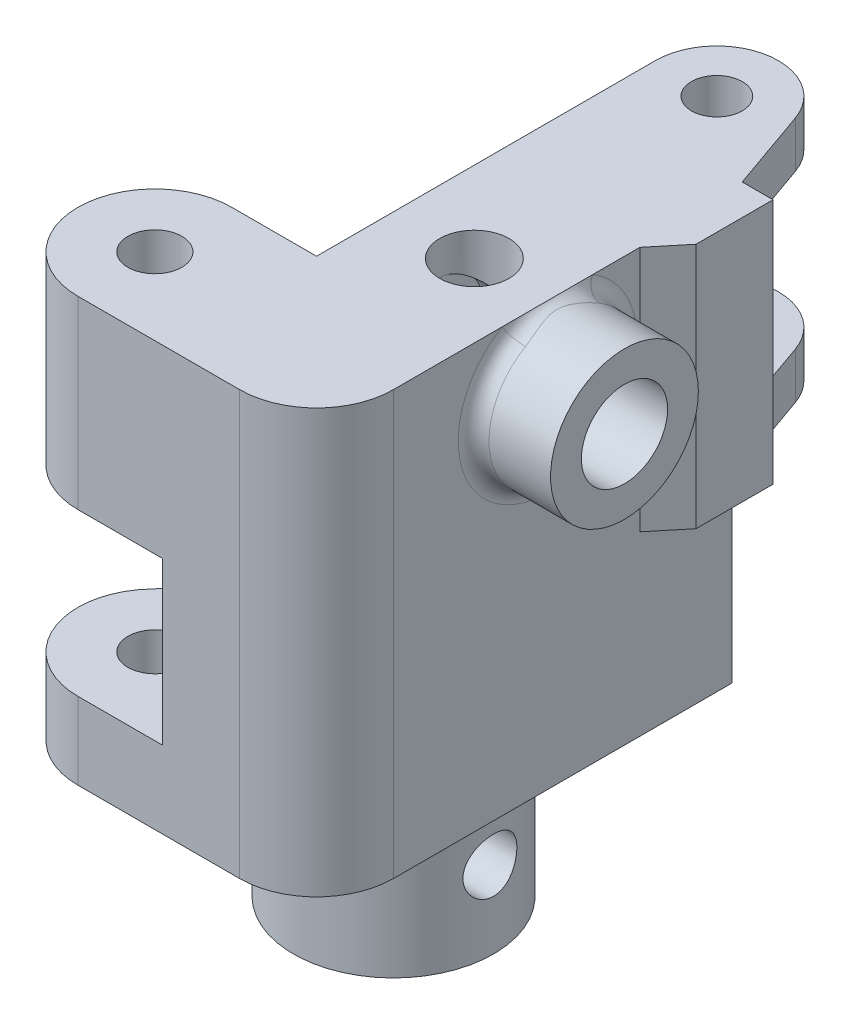
SolidWorks part; units mm, degrees
ref_plane "Front Plane" through (0, 0, 0) normal (0, 0, 1) x (1, 0, 0)
ref_plane "Top Plane" through (0, 0, 0) normal (0, 1, 0) x (1, 0, 0)
ref_plane "Right Plane" through (0, 0, 0) normal (1, 0, 0) x (0, 0, -1)
sketch "Sketch1" plane through (0, 0, 0) normal (0, 1, 0) x (1, 0, 0)
  line L0 (0, 0) -> (5.5, 0) construction
  line L1 (0, 5) -> (5.5, 5)
  line L2 (0, -5) -> (5.5, -5)
  line L3 (5.5, 5) -> (5.5, 22)
  line L4 (5.5, -5) -> (15.5, -5)
  line L6 (5.5, 22) -> (15.5, 22)
  line L7 (15.5, -5) -> (15.5, 22)
  line L8 (5.5, 20) -> (15.5, 20) construction
  arc A0 (0, 5) -> (0, -5) centre (0, 0) ccw
  circle A2 centre (0, 0) radius 1.75
  circle A3 centre (5.5, 10) radius 39 construction
  dimension "D1" = 5
  dimension "D2" = 3.5
  dimension "D5" = 78
  dimension "D3" = 5.5
  dimension "D4" = 10
  dimension "D6" = 10
  dimension "D7" = 10
  dimension "D8" = 2
extrude "Boss-Extrude1" add sketch "Sketch1" along normal blind 5
sketch "Sketch2" plane through (0, 5, 0) normal (0, 1, 0) x (1, 0, 0)
  line L1 (5.5, 22) -> (15.5, 22)
  line L2 (5.5, 22) -> (5.5, -5)
  line L3 (5.5, -5) -> (15.5, -5)
  line L4 (15.5, 22) -> (15.5, -5)
extrude "Boss-Extrude2" add sketch "Sketch2" along normal blind 10.5
sketch "Sketch3" plane through (0, 15.5, 0) normal (0, 1, 0) x (1, 0, 0)
  line L0 (5.5, 5) -> (15.5, 5)
  line L3 (5.5, -5) -> (5.5, 5)
  line L4 (5.5, 22) -> (5.5, -5)
  line L5 (5.5, -5) -> (15.5, -5)
  line L6 (15.5, -5) -> (15.5, 22)
  line L7 (15.5, 22) -> (5.5, 22)
  line L9 (5.5, -5) -> (15.5, -5)
  line L10 (15.5, -5) -> (15.5, 5)
  line L12 (5.5, 5) -> (0, 5)
  line L13 (0, -5) -> (5.5, -5)
  line L15 (5.5, 5) -> (0, 5)
  line L16 (0, -5) -> (5.5, -5)
  circle A0 centre (0, 0) radius 1.75 construction
  arc A1 (0, 5) -> (0, -5) centre (0, 0) ccw
  arc A2 (0, 5) -> (0, -5) centre (0, 0) ccw
  circle A3 centre (0, 0) radius 1.75
  dimension "D1" = 0
  dimension "D2" = 0
extrude "Boss-Extrude3" add sketch "Sketch3" along normal blind 5
fillet "Fillet1" radius 5 1 edges at (15.5, 10.25, 5)
sketch "Sketch4" plane through (15.5, 0, 0) normal (1, 0, 0) x (0, 0, -1)
  line L0 (1.75, 20.5) -> (-1.75, 20.5) construction
  line L1 (1.75, 20.5) -> (-1.75, 20.5)
  line L2 (0, 20.5) -> (0, 10.25) construction
  line L3 (0, 20.5) -> (0, 0) construction
  line L4 (0, 10.25) -> (20, 10.25) construction
  circle A0 centre (20, 10.25) radius 2.8 construction
  dimension "D2" = 5.6
  dimension "D1" = 20
extrude "Cut-Extrude1" [suppressed] cut sketch "Sketch4" against normal through all contours A0
sketch "Sketch5" plane through (0, 0, 0) normal (0, -1, 0) x (1, 0, 0)
  line L0 (5.5, -22) -> (5.5, -5) construction
  circle A0 centre (5.5, -10) radius 6.5
  circle A1 centre (0, 0) radius 1.75 construction
  circle A2 centre (0, 0) radius 1.75 construction
  circle A3 centre (5.5, -10) radius 2.5
  dimension "D2" = 13
  dimension "D3" = 5
  dimension "D1" = 10
extrude "Boss-Extrude4" add sketch "Sketch5" along normal blind 11
sketch "Sketch6" plane through (0, 0, 0) normal (0, 1, 0) x (1, 0, 0)
  line L3 (5.5, 12.5) -> (5.5, 16.5)
  line L4 (1.3467, 5) -> (5.5, 5)
  line L5 (5.5, 5) -> (5.5, 7.5)
  line L6 (5.5, 12.5) -> (5.5, 16.5)
  line L7 (1.3467, 5) -> (5.5, 5)
  line L8 (5.5, 5) -> (5.5, 7.5)
  arc A2 (5.5, 16.5) -> (1.3467, 5) centre (5.5, 10) ccw
  arc A3 (5.5, 12.5) -> (5.5, 7.5) centre (5.5, 10) ccw
  arc A4 (5.5, 16.5) -> (1.3467, 5) centre (5.5, 10) ccw
  arc A5 (5.5, 12.5) -> (5.5, 7.5) centre (5.5, 10) ccw
  dimension "D1" = 0
extrude "Boss-Extrude5" add sketch "Sketch6" along normal up to surface (5 mm away) up to face at (1.5, 5, 0)
sketch "Sketch7" plane through (0, 0, 0) normal (1, 0, 0) x (0, 0, -1)
  line L0 (10, -11) -> (10, -6) construction
  line L1 (3.5, -11) -> (16.5, -11) construction
  circle A0 centre (10, -6) radius 1.75
  dimension "D1" = 3.5
  dimension "D2" = 5
extrude "Cut-Extrude2" cut sketch "Sketch7" against normal through all both and the other way through all
sketch "Sketch8" [suppressed] plane through (15.5, 0, 0) normal (1, 0, 0) x (0, 0, -1)
  circle A0 centre (13.5, 10.25) radius 1.6
  circle A1 centre (26.5, 10.25) radius 1.6
  circle A2 centre (20, 10.25) radius 2.8 construction
  circle A3 centre (20, 10.25) radius 2.8 construction
  dimension "D2" = 3.2
  dimension "D3" = 3.2
  dimension "D1" = 6.5
  dimension "D4" = 6.5
extrude "Cut-Extrude3" [suppressed] cut sketch "Sketch8" against normal blind 8
fillet "Fillet2" [suppressed] radius 5
chamfer "Chamfer1" [suppressed] distance 1 angle 45
fillet "Fillet3" radius 5 1 edges at (10.5, 15.5, -5)
sketch "Sketch9" plane through (5.5, 0, 0) normal (-1, 0, 0) x (0, 0, 1)
  line L0 (-22, 15.5) -> (-10, 15.5) construction
  line L1 (-22, 15.5) -> (-5, 15.5)
  line L2 (-22, 15.5) -> (-22, 27.5)
  line L3 (-22, 27.5) -> (-5, 27.5)
  line L4 (-5, 15.5) -> (-5, 27.5)
  line L5 (-5, 20.5) -> (-5, 15.5) construction
  line L7 (-22, 15.5) -> (-22, 0) construction
  dimension "D1" = 12
extrude "Boss-Extrude6" add sketch "Sketch9" against normal up to surface (10 mm away) up to face at (15.5, 11.8274, -9.6607)
fillet "Fillet4" [suppressed] radius 4
fillet "Fillet5" [suppressed] radius 2
sketch "Sketch10" [suppressed] plane through (0, 27.5, 0) normal (0, 1, 0) x (1, 0, 0)
  line L0 (10.5, 11.1) -> (10.5, 7) construction
  line L1 (5.5, 7) -> (15.5, 7) construction
  line L2 (10.5, 11.1) -> (5.5, 11.1) construction
  line L3 (5.5, 7) -> (5.5, 15.2) construction
  line L5 (9.5, 13.35) -> (11.5, 13.35) construction
  line L6 (9.5, 13.35) -> (9.5, 8.85) construction
  line L7 (9.5, 8.85) -> (11.5, 8.85) construction
  line L8 (11.5, 13.35) -> (11.5, 8.85) construction
  line L9 (9.5, 13.35) -> (11.5, 8.85) construction
  line L10 (9.5, 8.85) -> (11.5, 13.35) construction
  circle A1 centre (10.5, 11.1) radius 2
  dimension "D1" = 4.5
  dimension "D3" = 4
  dimension "D2" = 2
extrude "Cut-Extrude4" [suppressed] cut sketch "Sketch10" against normal blind 10
sketch "Sketch11" plane through (15.5, 0, 0) normal (1, 0, 0) x (0, 0, -1)
  line L0 (10, 22.5) -> (10, 27.5) construction
  line L2 (5, 27.5) -> (5, 20.5) construction
  circle A0 centre (10, 22.5) radius 2.8
  dimension "D1" = 5.6
  dimension "D2" = 5
  dimension "D3" = 5
extrude "Cut-Extrude5" cut sketch "Sketch11" against normal blind 7
sketch "Sketch12" plane through (15.5, 0, 0) normal (1, 0, 0) x (0, 0, -1)
  circle A0 centre (10, 22.5) radius 2.8 construction
  circle A1 centre (10, 22.5) radius 2.8
  circle A2 centre (10, 22.5) radius 4.8
  dimension "D1" = 2
extrude "Boss-Extrude7" add sketch "Sketch12" along normal blind 5
chamfer "Chamfer2" distance 3 angle 45 1 edges at (5.5, -11, -12.5)
chamfer "Chamfer3" distance 3 angle 45 1 edges at (5.5, 0, -10)
fillet "Fillet6" radius 2 1 edges at (3, 5, -10)
sketch "Sketch13" [suppressed] plane through (5.5, 0, 0) normal (-1, 0, 0) x (0, 0, 1)
  line L0 (-26, 15.5) -> (-17.2, 15.5) construction
  line L1 (-26, 0) -> (-37, 0)
  line L2 (-26, 0) -> (-26, 15.5)
  line L3 (-26, 15.5) -> (-37, 15.5)
  line L4 (-41, 4) -> (-41, 11.5)
  line L5 (-16.5, 5) -> (-16.5, 0) construction
  circle A0 centre (-35, 10.25) radius 2.8
  arc A3 (-37, 0) -> (-41, 4) centre (-37, 4) cw
  arc A4 (-37, 15.5) -> (-41, 11.5) centre (-37, 11.5) ccw
  dimension "D1" = 5.6
  dimension "D3" = 4
  dimension "D2" = 18.5
  dimension "D4" = 6
  dimension "D5" = 10.25
extrude "Boss-Extrude8" [suppressed] add sketch "Sketch13" against normal up to surface (10 mm away)
sketch "Sketch14" plane through (0, 20.5, 0) normal (0, 1, 0) x (1, 0, 0)
  line L4 (0, -5) -> (10.5, -5)
  line L5 (15.5, 0) -> (15.5, 5)
  line L6 (15.5, 5) -> (5.5, 5)
  line L7 (5.5, 5) -> (0, 5)
  line L8 (0, -5) -> (10.5, -5)
  line L9 (15.5, 0) -> (15.5, 5)
  line L11 (5.5, 5) -> (0, 5)
  line L13 (15.5, 5) -> (5.5, 5)
  circle A0 centre (0, 0) radius 1.75 construction
  circle A1 centre (0, 0) radius 1.75
  arc A2 (10.5, -5) -> (15.5, 0) centre (10.5, 0) ccw
  arc A3 (0, 5) -> (0, -5) centre (0, 0) ccw
  arc A4 (10.5, -5) -> (15.5, 0) centre (10.5, 0) ccw
  arc A5 (0, 5) -> (0, -5) centre (0, 0) ccw
  dimension "D1" = 0
extrude "Boss-Extrude9" add sketch "Sketch14" along normal up to surface (7 mm away) up to face at (10.5, 27.5, -13.5)
fillet "Fillet7" radius 10 1 edges at (1.3467, 2.5, -5)
fillet "Fillet8" [suppressed] radius 5
sketch "Sketch15" plane through (0, 27.5, 0) normal (0, 1, 0) x (1, 0, 0)
  line L0 (8.5, 7.2) -> (8.5, 12.8) construction
  line L1 (8.5, 7.2) -> (8.5, 12.8) construction
  line L2 (10.75, 10) -> (8.5, 10) construction
  circle A0 centre (10.75, 10) radius 2.25
  dimension "D1" = 4.5
extrude "Cut-Extrude6" cut sketch "Sketch15" against normal blind 10
fillet "Fillet9" radius 1 1 edges at (15.5, 22.5, -5.2)
sketch "Sketch16" plane through (0, 27.5, 0) normal (0, 1, 0) x (1, 0, 0)
  line L0 (5.5, 22) -> (5.5, 27)
  line L1 (13.2732, 28.3278) -> (15.5, 22)
  line L2 (5.5, 22) -> (15.5, 22)
  circle A0 centre (9.5, 27) radius 1.65
  arc A1 (13.2732, 28.3278) -> (5.5, 27) centre (9.5, 27) ccw
  dimension "D1" = 3.3
  dimension "D2" = 8
  dimension "D3" = 5
extrude "Boss-Extrude10" add sketch "Sketch16" against normal blind 16
ref_plane "Plane1" through (0, 19.5, 0) normal (0, 1, 0) x (1, 0, 0)
sketch "Sketch17" plane through (0, 19.5, 0) normal (0, 1, 0) x (1, 0, 0)
  line L0 (15.5, 22) -> (5.5, 22)
  line L1 (5.5, 5) -> (5.5, 27) construction
  line L9 (15.5, 12.9394) -> (15.5, 22)
  line L10 (15.5, 22) -> (13.2732, 28.3278)
  line L11 (5.5, 27) -> (5.5, 5)
  line L12 (5.5, 5) -> (0, 5)
  line L13 (0, -5) -> (10.5, -5)
  line L14 (15.5, 0) -> (15.5, 7.0606)
  line L15 (15.5, 7.0606) -> (15.5, 12.9394)
  line L17 (15.5, 22) -> (13.2732, 28.3278)
  line L18 (5.5, 27) -> (5.5, 22)
  arc A3 (13.2732, 28.3278) -> (5.5, 27) centre (9.5, 27) ccw
  arc A4 (0, 5) -> (0, -5) centre (0, 0) ccw
  arc A5 (10.5, -5) -> (15.5, 0) centre (10.5, 0) ccw
  arc A6 (13.2732, 28.3278) -> (5.5, 27) centre (9.5, 27) ccw
  dimension "D1" = 0
extrude "Cut-Extrude7" cut sketch "Sketch17" against normal blind 5 and the other way blind 5
sketch "Sketch18" plane through (0, 27.5, 0) normal (0, 1, 0) x (1, 0, 0)
  line L0 (15.5, 22) -> (13.2732, 28.3278) construction
  line L1 (15.1481, 23) -> (17.1481, 23)
  line L2 (15.1481, 23) -> (15.1481, 18)
  line L4 (17.1481, 23) -> (17.1481, 18)
  line L5 (17.1481, 18) -> (15.5, 16)
  line L6 (15.5, 22) -> (15.5, 12.9394) construction
  line L7 (15.5, 16) -> (15.1481, 18)
  dimension "D1" = 1
  dimension "D2" = 2
  dimension "D3" = 2
  dimension "D4" = 4
extrude "Boss-Extrude11" add sketch "Sketch18" against normal up to surface (16 mm away) up to face at (9.5, 11.5, -25.35)
